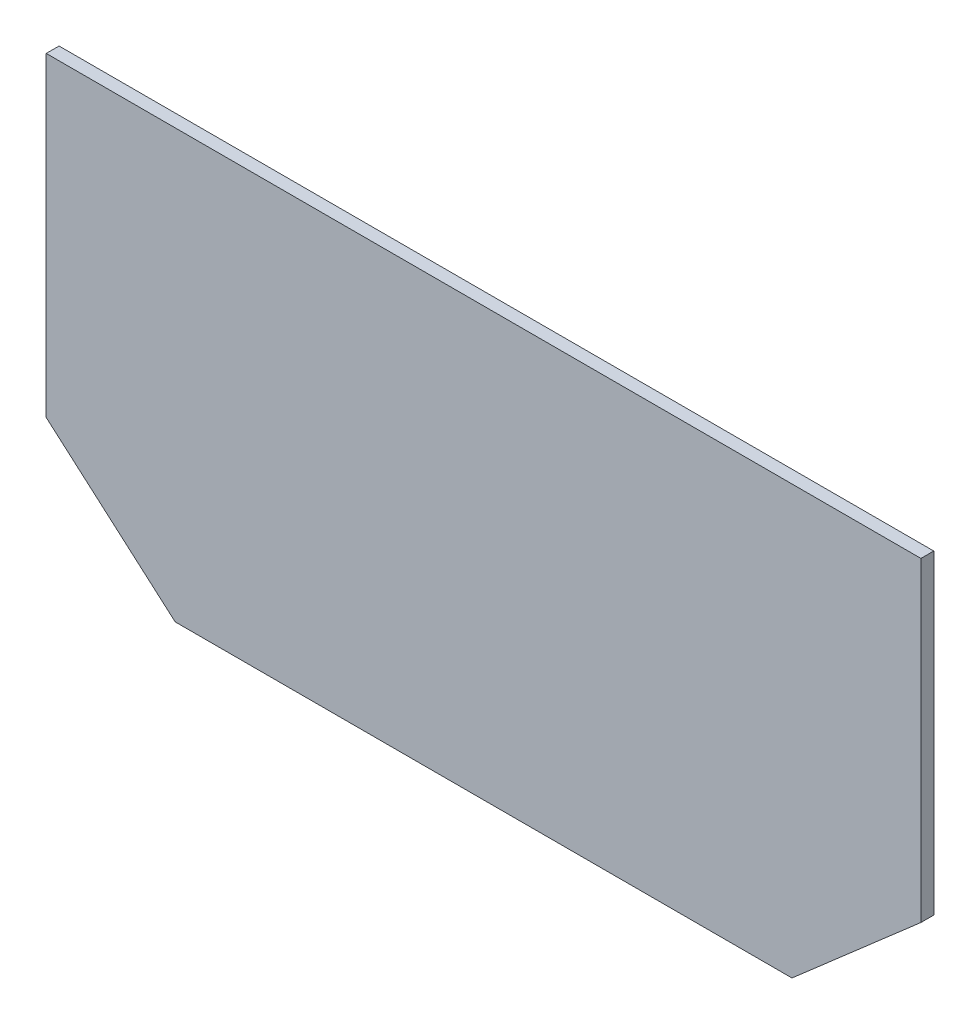
SolidWorks part; units mm, degrees
material "AISI 1020"
ref_plane "Спереди" through (0, 0, 0) normal (0, 0, 1) x (1, 0, 0)
ref_plane "Сверху" through (0, 0, 0) normal (0, 1, 0) x (1, 0, 0)
ref_plane "Справа" through (0, 0, 0) normal (1, 0, 0) x (0, 0, -1)
sketch "Эскиз1" plane through (0, 0, 0) normal (0, 0, 1) x (1, 0, 0)
  line L1 (-204.4377, -50) -> (204.4377, -50)
  line L2 (-204.4377, -50) -> (-204.4377, -197.4021)
  line L3 (-144.1595, -250) -> (144.1595, -250)
  line L4 (204.4377, -50) -> (204.4377, -197.4021)
  line L5 (-204.4377, -197.4021) -> (-144.1595, -250)
  line L6 (204.4377, -197.4021) -> (144.1595, -250)
  line L7 (-1942.3038, -100) -> (2192.0181, -100) construction
  line L8 (-2154.3442, -2492.8737) -> (-37.6739, -67.1263) construction
  line L9 (37.6739, -67.1263) -> (2154.3442, -2492.8737) construction
  line L10 (33.1795, -100) -> (2092.4797, -2460) construction
  line L11 (0, -100) -> (0, -250) construction
  point P13 (174.2986, -223.7011)
  point P16 (-174.2986, -223.7011)
  point P22 (0, -50)
  dimension "D1" = 50
  dimension "D2" = 15
  dimension "D3" = 200
base flange "Базовая кромка1" sketch "Эскиз1" thickness 6 reverse thickness direction yes parameters "D1"=0.75
sketch "Сгиб-Линии1" plane through (0, 0, 0) normal (0, 1, 0) x (1, 0, 0)
sketch "Граничная рамка1" plane through (0, 0, 0) normal (0, 1, 0) x (1, 0, 0)
sheet metal parameters "Листовой металл3" thickness 6 parameters "D1"=0.75
flat pattern "Развертка3" [suppressed]
sketch "Сгиб-Линии2" plane through (0, 0, 0) normal (0, 1, 0) x (1, 0, 0)
sketch "Граничная рамка2" [suppressed] plane through (0, 0, 0) normal (0, 1, 0) x (1, 0, 0)
